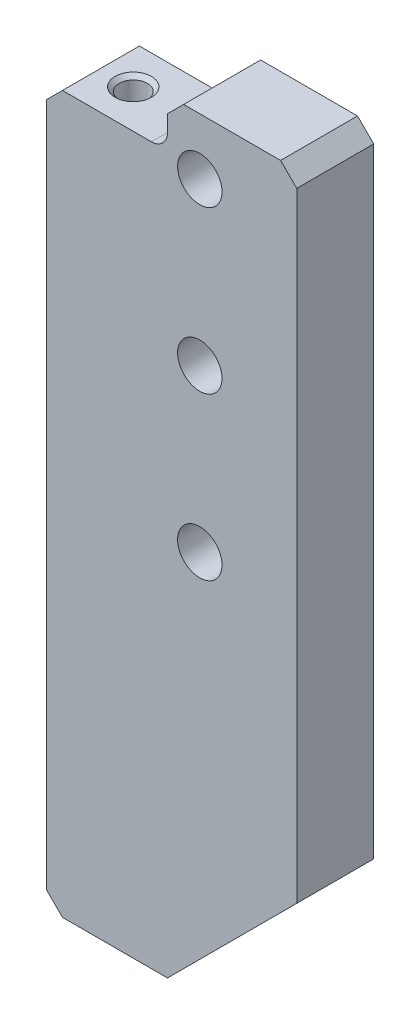
SolidWorks part; units mm, degrees
material "Plain Carbon Steel"
ref_plane "Front Plane" through (0, 0, 0) normal (0, 0, 1) x (1, 0, 0)
ref_plane "Top Plane" through (0, 0, 0) normal (0, 1, 0) x (1, 0, 0)
ref_plane "Right Plane" through (0, 0, 0) normal (1, 0, 0) x (0, 0, -1)
sketch "Sketch1" plane through (0, 0, 0) normal (0, 0, 1) x (1, 0, 0)
  line L1 (-176.2477, 107.1924) -> (-176.2477, 18.5523) construction
  line L2 (-176.2477, 107.1924) -> (-161.2477, 107.1924) construction
  line L3 (-161.2477, 107.1924) -> (-161.2477, 113.1924) construction
  line L4 (-161.2477, 113.1924) -> (-145.2477, 113.1924) construction
  line L5 (-145.2477, 113.1924) -> (-145.2477, 34.5523) construction
  line L7 (-168.7477, 118.1924) -> (-168.7477, 107.1924) construction
  line L8 (-170.2477, 118.1924) -> (-170.2477, 107.1924) construction
  line L9 (-171.7477, 118.1924) -> (-171.7477, 107.1924) construction
  line L10 (-161.2477, 18.5523) -> (-176.2477, 18.5523)
  line L11 (-176.2477, 107.1924) -> (-176.2477, 18.5523)
  line L12 (-176.2477, 107.1924) -> (-161.2477, 107.1924)
  line L13 (-161.2477, 107.1924) -> (-161.2477, 113.1924)
  line L14 (-161.2477, 113.1924) -> (-145.2477, 113.1924)
  line L15 (-145.2477, 113.1924) -> (-145.2477, 34.5523)
  line L16 (-145.2477, 34.5523) -> (-161.2477, 18.5523)
  line L17 (-168.7477, 118.1924) -> (-168.7477, 107.1924) construction
  line L18 (-170.2477, 118.1924) -> (-170.2477, 107.1924) construction
  line L19 (-171.7477, 118.1924) -> (-171.7477, 107.1924) construction
  line L20 (-168.7477, 107.1924) -> (-168.7477, 87.1924) construction
  line L21 (-168.7477, 87.1924) -> (-170.2477, 86.3264) construction
  line L22 (-170.2477, 86.3264) -> (-171.7477, 87.1924) construction
  line L23 (-171.7477, 87.1924) -> (-171.7477, 107.1924) construction
  line L24 (-168.7477, 87.1924) -> (-171.7477, 87.1924) construction
  circle A0 centre (-157.2477, 66.1924) radius 2.75 construction
  circle A1 centre (-157.2477, 86.1924) radius 2.75 construction
  circle A2 centre (-157.2477, 106.1924) radius 2.75 construction
  circle A3 centre (-169.2477, 106.1924) radius 2.75 construction
  circle A4 centre (-157.2477, 66.1924) radius 2.75
  circle A5 centre (-157.2477, 86.1924) radius 2.75
  circle A6 centre (-157.2477, 106.1924) radius 2.75
  circle A7 centre (-169.2477, 106.1924) radius 2.75 construction
  dimension "D1" = 120
  dimension "D2" = 20
extrude "Boss-Extrude1" add sketch "Sketch1" along normal blind 4.7625 and the other way blind 4.7625
sketch "Sketch2" plane through (0, 0, 0) normal (0, 0, 1) x (1, 0, 0)
  line L0 (-170.2477, 107.1924) -> (-171.9977, 107.1924)
  line L1 (-171.9977, 107.1924) -> (-171.9977, 102.1924)
  line L2 (-171.9977, 102.1924) -> (-171.4477, 101.8748)
  line L3 (-171.4477, 101.8748) -> (-171.4477, 87.0192)
  line L4 (-171.4477, 87.0192) -> (-170.2477, 86.3264)
  line L5 (-170.2477, 107.1924) -> (-170.2477, 86.3264)
  line L6 (-161.2477, 107.1924) -> (-176.2477, 107.1924) construction
  line L7 (-170.2477, 107.1924) -> (-170.2477, 95.5113) construction
  line L8 (-176.2477, 107.1924) -> (-161.2477, 107.1924) construction
  line L9 (-170.2477, 118.1924) -> (-170.2477, 107.1924) construction
  line L10 (-170.2477, 86.3264) -> (-171.7477, 87.1924) construction
  dimension "D1" = 3.5
  dimension "D2" = 5
  dimension "D3" = 2.4
revolve "Cut-Revolve1" cut sketch "Sketch2" angle 360 about L7
chamfer "Chamfer1" distance 2 angle 45 4 edges at (-176.2477, 18.5523, 0) (-145.2477, 113.1924, 0) (-161.2477, 113.1924, 0) (-176.2477, 107.1924, 0)
chamfer "Chamfer2" distance 0.5 angle 45 1 edges at (-170.2477, 107.1924, 1.75)
fillet "Fillet1" radius 2 1 edges at (-161.2477, 107.1924, 0)
